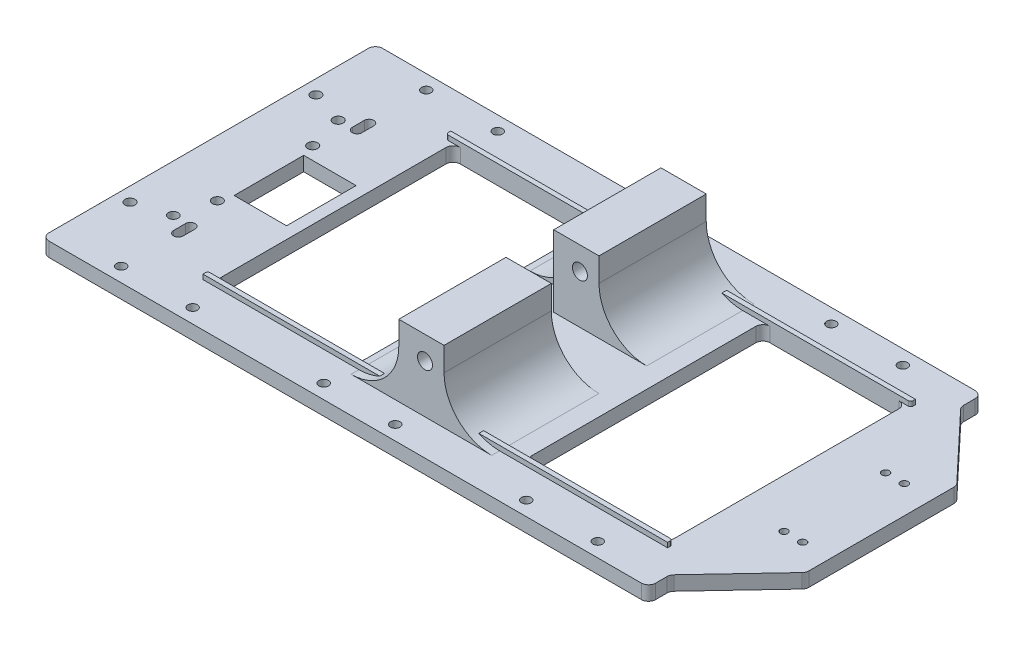
SolidWorks part; units mm, degrees
ref_plane "前视基准面" through (0, 0, 0) normal (0, 0, 1) x (1, 0, 0)
ref_plane "上视基准面" through (0, 0, 0) normal (0, 1, 0) x (1, 0, 0)
ref_plane "右视基准面" through (0, 0, 0) normal (1, 0, 0) x (0, 0, -1)
sketch "草图1" plane through (0, 0, 0) normal (0, 1, 0) x (1, 0, 0)
  line L0 (4082.7289, 1509.8503) -> (4060.7289, 1509.8503)
  line L1 (4175.7346, 1460.2503) -> (4175.7346, 1455.2395)
  line L2 (4145.7346, 1460.2503) -> (4145.7346, 1455.2395)
  line L3 (4179.7346, 1455.2395) -> (4179.7346, 1460.2503)
  line L4 (4115.6347, 1530.6257) -> (4120.1638, 1528.0129)
  line L5 (4060.7289, 1480.6503) -> (4082.7289, 1480.6503)
  line L6 (4094.7346, 1455.2395) -> (4094.7346, 1460.2503)
  line L7 (4149.7346, 1455.2395) -> (4149.7346, 1460.2503)
  line L8 (4122.2625, 1531.6509) -> (4117.7334, 1534.2637)
  line L9 (4060.7346, 1460.2503) -> (4060.7346, 1455.2395)
  line L10 (4234.7346, 1455.2395) -> (4234.7346, 1460.2503)
  line L11 (4064.7346, 1455.2395) -> (4064.7346, 1460.2503)
  line L12 (4090.7346, 1460.2503) -> (4090.7346, 1455.2395)
  line L13 (4060.7289, 1509.8503) -> (4060.7289, 1480.6503)
  line L14 (4082.7289, 1480.6503) -> (4082.7289, 1509.8503)
  line L15 (4090.7346, 1530.2503) -> (4090.7346, 1535.2611)
  line L16 (4176.5776, 1504.5503) -> (4176.5776, 1485.9503)
  line L17 (4175.5776, 1484.9503) -> (4135.5776, 1484.9503)
  line L18 (4094.7346, 1535.2611) -> (4094.7346, 1530.2503)
  line L19 (4115.7772, 1460.3388) -> (4120.3279, 1462.5177)
  line L20 (4149.7346, 1535.2611) -> (4149.7346, 1530.2503)
  line L21 (4060.7346, 1530.2503) -> (4060.7346, 1535.2611)
  line L22 (4145.7346, 1530.2503) -> (4145.7346, 1535.2611)
  line L23 (4122.1349, 1458.8376) -> (4117.6283, 1456.569)
  line L24 (4134.5776, 1485.9503) -> (4134.5776, 1504.5503)
  line L25 (4135.5776, 1505.5503) -> (4175.5776, 1505.5503)
  line L26 (4064.7346, 1535.2611) -> (4064.7346, 1530.2503)
  line L27 (4175.7346, 1530.2503) -> (4175.7346, 1535.2611)
  line L28 (4038.4346, 1425.2395) -> (4287.0345, 1425.2395)
  line L29 (4317.7347, 1464.8467) -> (4317.7347, 1525.6539)
  line L30 (4251.291, 1514.7632) -> (4251.291, 1522.5539)
  line L31 (4251.291, 1542.4908) -> (4251.291, 1550.2815)
  line L32 (4260.7346, 1460.2503) -> (4260.7346, 1455.2395)
  line L33 (4264.7346, 1455.2395) -> (4264.7346, 1460.2503)
  line L34 (4287.0345, 1565.2611) -> (4038.4346, 1565.2611)
  line L35 (4248.191, 1550.2815) -> (4248.191, 1542.4908)
  line L36 (4035.4346, 1562.2611) -> (4035.4346, 1428.2395)
  line L37 (4316.9188, 1527.7105) -> (4290.8504, 1555.3947)
  line L38 (4290.0345, 1557.4513) -> (4290.0345, 1562.2611)
  line L39 (4290.8504, 1435.106) -> (4316.9188, 1462.7901)
  line L40 (4248.191, 1522.5539) -> (4248.191, 1514.7632)
  line L41 (4230.7346, 1460.2503) -> (4230.7346, 1455.2395)
  line L42 (4290.0345, 1428.2395) -> (4290.0345, 1433.0493)
  line L43 (4256.0776, 1504.5503) -> (4256.0776, 1485.9503)
  line L44 (4230.7346, 1530.2503) -> (4230.7346, 1535.2611)
  line L45 (4260.7346, 1530.2503) -> (4260.7346, 1535.2611)
  line L46 (4255.0776, 1484.9503) -> (4215.0776, 1484.9503)
  line L47 (4215.0776, 1505.5503) -> (4255.0776, 1505.5503)
  line L48 (4179.7346, 1535.2611) -> (4179.7346, 1530.2503)
  line L49 (4248.191, 1467.9468) -> (4248.191, 1475.7374)
  line L50 (4234.7346, 1535.2611) -> (4234.7346, 1530.2503)
  line L51 (4214.0776, 1485.9503) -> (4214.0776, 1504.5503)
  line L52 (4248.191, 1440.2192) -> (4248.191, 1448.0098)
  line L53 (4251.291, 1475.7374) -> (4251.291, 1467.9468)
  line L54 (4264.7346, 1535.2611) -> (4264.7346, 1530.2503)
  line L55 (4251.291, 1448.0098) -> (4251.291, 1440.2192)
  arc A0 (4149.7346, 1460.2503) -> (4145.7346, 1460.2503) centre (4147.7346, 1460.2503) ccw
  arc A1 (4175.7346, 1455.2395) -> (4179.7346, 1455.2395) centre (4177.7346, 1455.2395) ccw
  arc A2 (4060.7346, 1455.2395) -> (4064.7346, 1455.2395) centre (4062.7346, 1455.2395) ccw
  circle A3 centre (4041.3063, 1456.3883) radius 2.1
  arc A4 (4064.7346, 1460.2503) -> (4060.7346, 1460.2503) centre (4062.7346, 1460.2503) ccw
  arc A5 (4179.7346, 1460.2503) -> (4175.7346, 1460.2503) centre (4177.7346, 1460.2503) ccw
  arc A6 (4090.7346, 1455.2395) -> (4094.7346, 1455.2395) centre (4092.7346, 1455.2395) ccw
  arc A7 (4230.7346, 1455.2395) -> (4234.7346, 1455.2395) centre (4232.7346, 1455.2395) ccw
  arc A8 (4117.7334, 1534.2637) -> (4115.6347, 1530.6257) centre (4116.6841, 1532.4447) ccw
  circle A9 centre (4055.2132, 1460.6687) radius 2.05
  arc A10 (4145.7346, 1455.2395) -> (4149.7346, 1455.2395) centre (4147.7346, 1455.2395) ccw
  circle A11 centre (4041.3063, 1534.3883) radius 2.1
  arc A12 (4094.7346, 1460.2503) -> (4090.7346, 1460.2503) centre (4092.7346, 1460.2503) ccw
  circle A13 centre (4055.2132, 1529.8319) radius 2.1
  circle A14 centre (4059.1243, 1515.2233) radius 2.1
  circle A15 centre (4059.1243, 1475.2233) radius 2.1
  arc A16 (4120.1638, 1528.0129) -> (4122.2625, 1531.6509) centre (4121.2132, 1529.8319) ccw
  arc A17 (4149.7346, 1535.2611) -> (4145.7346, 1535.2611) centre (4147.7346, 1535.2611) ccw
  arc A18 (4134.5776, 1485.9503) -> (4135.5776, 1484.9503) centre (4135.5776, 1485.9503) ccw
  arc A19 (4122.1349, 1458.8376) -> (4120.3279, 1462.5177) centre (4121.2132, 1460.6687) ccw
  arc A20 (4094.7346, 1535.2611) -> (4090.7346, 1535.2611) centre (4092.7346, 1535.2611) ccw
  arc A21 (4145.7346, 1530.2503) -> (4149.7346, 1530.2503) centre (4147.7346, 1530.2503) ccw
  arc A22 (4064.7346, 1535.2611) -> (4060.7346, 1535.2611) centre (4062.7346, 1535.2611) ccw
  circle A23 centre (4298.1991, 1473.9374) radius 1.55
  arc A24 (4060.7346, 1530.2503) -> (4064.7346, 1530.2503) centre (4062.7346, 1530.2503) ccw
  arc A25 (4175.5776, 1484.9503) -> (4176.5776, 1485.9503) centre (4175.5776, 1485.9503) ccw
  arc A26 (4115.7772, 1460.3388) -> (4117.6283, 1456.569) centre (4116.6841, 1458.4447) ccw
  circle A27 centre (4262.7346, 1559.2611) radius 2
  arc A28 (4090.7346, 1530.2503) -> (4094.7346, 1530.2503) centre (4092.7346, 1530.2503) ccw
  circle A29 centre (4306.0131, 1516.5632) radius 1.55
  circle A30 centre (4259.8276, 1500.2503) radius 1.6
  arc A31 (4176.5776, 1504.5503) -> (4175.5776, 1505.5503) centre (4175.5776, 1504.5503) ccw
  circle A32 centre (4298.1991, 1516.5632) radius 1.55
  circle A33 centre (4262.7346, 1431.2395) radius 2
  circle A34 centre (4306.0131, 1473.9374) radius 1.55
  arc A35 (4135.5776, 1505.5503) -> (4134.5776, 1504.5503) centre (4135.5776, 1504.5503) ccw
  arc A36 (4290.0345, 1562.2611) -> (4287.0345, 1565.2611) centre (4287.0345, 1562.2611) ccw
  arc A37 (4248.191, 1514.7632) -> (4251.291, 1514.7632) centre (4249.741, 1514.7632) ccw
  arc A38 (4038.4346, 1565.2611) -> (4035.4346, 1562.2611) centre (4038.4346, 1562.2611) ccw
  arc A39 (4264.7346, 1460.2503) -> (4260.7346, 1460.2503) centre (4262.7346, 1460.2503) ccw
  arc A40 (4317.7347, 1525.6539) -> (4316.9188, 1527.7105) centre (4314.7347, 1525.6539) ccw
  arc A41 (4234.7346, 1460.2503) -> (4230.7346, 1460.2503) centre (4232.7346, 1460.2503) ccw
  arc A42 (4248.191, 1542.4908) -> (4251.291, 1542.4908) centre (4249.741, 1542.4908) ccw
  arc A43 (4290.0345, 1557.4513) -> (4290.8504, 1555.3947) centre (4293.0345, 1557.4513) ccw
  arc A44 (4251.291, 1522.5539) -> (4248.191, 1522.5539) centre (4249.741, 1522.5539) ccw
  arc A45 (4035.4346, 1428.2395) -> (4038.4346, 1425.2395) centre (4038.4346, 1428.2395) ccw
  arc A46 (4251.291, 1550.2815) -> (4248.191, 1550.2815) centre (4249.741, 1550.2815) ccw
  arc A47 (4287.0345, 1425.2395) -> (4290.0345, 1428.2395) centre (4287.0345, 1428.2395) ccw
  arc A48 (4290.8504, 1435.106) -> (4290.0345, 1433.0493) centre (4293.0345, 1433.0493) ccw
  arc A49 (4316.9188, 1462.7901) -> (4317.7347, 1464.8467) centre (4314.7347, 1464.8467) ccw
  arc A50 (4260.7346, 1455.2395) -> (4264.7346, 1455.2395) centre (4262.7346, 1455.2395) ccw
  arc A51 (4234.7346, 1535.2611) -> (4230.7346, 1535.2611) centre (4232.7346, 1535.2611) ccw
  arc A52 (4214.0776, 1485.9503) -> (4215.0776, 1484.9503) centre (4215.0776, 1485.9503) ccw
  arc A53 (4260.7346, 1530.2503) -> (4264.7346, 1530.2503) centre (4262.7346, 1530.2503) ccw
  arc A54 (4230.7346, 1530.2503) -> (4234.7346, 1530.2503) centre (4232.7346, 1530.2503) ccw
  arc A55 (4255.0776, 1484.9503) -> (4256.0776, 1485.9503) centre (4255.0776, 1485.9503) ccw
  arc A56 (4179.7346, 1535.2611) -> (4175.7346, 1535.2611) centre (4177.7346, 1535.2611) ccw
  arc A57 (4215.0776, 1505.5503) -> (4214.0776, 1504.5503) centre (4215.0776, 1504.5503) ccw
  arc A58 (4256.0776, 1504.5503) -> (4255.0776, 1505.5503) centre (4255.0776, 1504.5503) ccw
  arc A59 (4251.291, 1475.7374) -> (4248.191, 1475.7374) centre (4249.741, 1475.7374) ccw
  arc A60 (4175.7346, 1530.2503) -> (4179.7346, 1530.2503) centre (4177.7346, 1530.2503) ccw
  arc A61 (4251.291, 1448.0098) -> (4248.191, 1448.0098) centre (4249.741, 1448.0098) ccw
  arc A62 (4264.7346, 1535.2611) -> (4260.7346, 1535.2611) centre (4262.7346, 1535.2611) ccw
  arc A63 (4248.191, 1467.9468) -> (4251.291, 1467.9468) centre (4249.741, 1467.9468) ccw
  arc A64 (4248.191, 1440.2192) -> (4251.291, 1440.2192) centre (4249.741, 1440.2192) ccw
  circle A65 centre (4147.7346, 1559.2611) radius 2
  circle A66 centre (4232.7346, 1559.2611) radius 2
  circle A67 centre (4210.3276, 1500.2503) radius 1.6
  circle A68 centre (4101.3063, 1456.3883) radius 2.1
  circle A69 centre (4163.6841, 1458.4447) radius 2.1
  circle A70 centre (4133.2132, 1525.2503) radius 2.1
  circle A71 centre (4163.6841, 1532.4447) radius 2.1
  circle A72 centre (4101.3063, 1534.3883) radius 2.1
  circle A73 centre (4177.7346, 1431.2395) radius 2
  circle A74 centre (4155.2132, 1525.2503) radius 2.1
  circle A75 centre (4155.2132, 1465.2503) radius 2.1
  circle A76 centre (4130.8276, 1490.2503) radius 1.6
  circle A77 centre (4117.1639, 1516.3492) radius 1.5
  circle A78 centre (4181.1639, 1474.3492) radius 1.5
  circle A79 centre (4133.2132, 1465.2503) radius 2.1
  circle A80 centre (4062.7346, 1559.2611) radius 2
  circle A81 centre (4180.3276, 1490.2503) radius 1.6
  circle A82 centre (4099.1243, 1515.2233) radius 2.1
  circle A83 centre (4099.1243, 1475.2233) radius 2.1
  circle A84 centre (4181.1639, 1516.2592) radius 1.5
  circle A85 centre (4259.8276, 1490.2503) radius 1.6
  circle A86 centre (4147.7346, 1431.2395) radius 2
  circle A87 centre (4177.7346, 1559.2611) radius 2
  circle A88 centre (4130.8276, 1500.2503) radius 1.6
  circle A89 centre (4210.3276, 1490.2503) radius 1.6
  circle A90 centre (4180.3276, 1500.2503) radius 1.6
  circle A91 centre (4092.7346, 1559.2611) radius 2
  circle A92 centre (4117.1639, 1474.3492) radius 1.5
  circle A93 centre (4249.741, 1457.9783) radius 6
  circle A94 centre (4232.7346, 1431.2395) radius 2
  circle A95 centre (4092.7346, 1431.2395) radius 2
  circle A96 centre (4062.7346, 1431.2395) radius 2
  dimension "D1" = 140.0216
extrude "凸台-拉伸1" add sketch "草图1" along normal blind 6
sketch "草图3" plane through (0, 6, 0) normal (0, 1, 0) x (1, 0, 0)
  line L1 (4084.8148, 1551.9432) -> (4288.3985, 1551.9432)
  line L2 (4084.8148, 1551.9432) -> (4084.8148, 1435.8117)
  line L3 (4084.8148, 1435.8117) -> (4288.3985, 1435.8117)
  line L4 (4288.3985, 1551.9432) -> (4288.3985, 1435.8117)
extrude "凸台-拉伸2" add sketch "草图3" against normal blind 6 contours L4 L1 L2 L3 | L1 region at (4186.6066, 6, -1493.8775)
sketch "草图4" plane through (0, 6, 0) normal (0, 1, 0) x (1, 0, 0)
  line L1 (4317.7347, 1464.8467) -> (4317.7347, 1525.6539) construction
  line L2 (4090.7347, 1545.5452) -> (4144.7347, 1545.5452)
  line L3 (4087.7347, 1542.5452) -> (4087.7347, 1448.5452)
  line L4 (4090.7347, 1445.5452) -> (4144.7347, 1445.5452)
  line L5 (4147.7347, 1542.5452) -> (4147.7347, 1448.5452)
  line L7 (4220.7347, 1545.5452) -> (4274.7347, 1545.5452)
  line L8 (4217.7347, 1542.5452) -> (4217.7347, 1448.5452)
  line L9 (4220.7347, 1445.5452) -> (4274.7347, 1445.5452)
  line L10 (4277.7347, 1542.5452) -> (4277.7347, 1448.5452)
  arc A0 (4147.7347, 1448.5452) -> (4144.7347, 1445.5452) centre (4144.7347, 1448.5452) cw
  arc A1 (4090.7347, 1445.5452) -> (4087.7347, 1448.5452) centre (4090.7347, 1448.5452) cw
  arc A2 (4087.7347, 1542.5452) -> (4090.7347, 1545.5452) centre (4090.7347, 1542.5452) cw
  arc A3 (4144.7347, 1545.5452) -> (4147.7347, 1542.5452) centre (4144.7347, 1542.5452) cw
  arc A4 (4220.7347, 1445.5452) -> (4217.7347, 1448.5452) centre (4220.7347, 1448.5452) cw
  arc A5 (4277.7347, 1448.5452) -> (4274.7347, 1445.5452) centre (4274.7347, 1448.5452) cw
  arc A6 (4277.7347, 1542.5452) -> (4274.7347, 1545.5452) centre (4274.7347, 1542.5452) ccw
  arc A7 (4220.7347, 1545.5452) -> (4217.7347, 1542.5452) centre (4220.7347, 1542.5452) ccw
  point P8 (4147.7347, 1445.5452)
  point P13 (4087.7347, 1545.5452)
  point P16 (4147.7347, 1545.5452)
  point P23 (4217.7347, 1445.5452)
  point P26 (4277.7347, 1445.5452)
  dimension "D4" = 3
  dimension "D7" = 3
  dimension "D1" = 60
  dimension "D2" = 170
  dimension "D3" = 100
  dimension "D5" = 70
  dimension "D6" = 60
extrude "切除-拉伸1" cut sketch "草图4" against normal through all both and the other way through all
sketch "草图6" plane through (0, 6, 0) normal (0, 1, 0) x (1, 0, 0)
  line L0 (4087.7347, 1542.5452) -> (4087.7347, 1448.5452) construction
  line L1 (4085.7347, 1545.5452) -> (4278.7347, 1545.5452)
  line L2 (4084.7347, 1546.5452) -> (4084.7347, 1547.5452)
  line L3 (4084.7347, 1547.5452) -> (4279.7347, 1547.5452)
  line L4 (4279.7347, 1546.5452) -> (4279.7347, 1547.5452)
  line L5 (4277.7347, 1448.5452) -> (4277.7347, 1542.5452) construction
  line L6 (4087.7347, 1495.5452) -> (4196.6431, 1495.5452) construction
  line L7 (4279.7347, 1444.5452) -> (4279.7347, 1443.5452)
  line L8 (4084.7347, 1443.5452) -> (4279.7347, 1443.5452)
  line L9 (4084.7347, 1444.5452) -> (4084.7347, 1443.5452)
  line L10 (4085.7347, 1445.5452) -> (4278.7347, 1445.5452)
  arc A0 (4279.7347, 1546.5452) -> (4278.7347, 1545.5452) centre (4278.7347, 1546.5452) cw
  arc A1 (4085.7347, 1545.5452) -> (4084.7347, 1546.5452) centre (4085.7347, 1546.5452) cw
  arc A2 (4085.7347, 1445.5452) -> (4084.7347, 1444.5452) centre (4085.7347, 1444.5452) ccw
  arc A3 (4279.7347, 1444.5452) -> (4278.7347, 1445.5452) centre (4278.7347, 1444.5452) ccw
  point P10 (4279.7347, 1545.5452)
  point P23 (4279.7347, 1445.5452)
  dimension "D4" = 1
  dimension "D1" = 3
  dimension "D2" = 2
  dimension "D3" = 2
extrude "凸台-拉伸3" add sketch "草图6" along normal blind 2
sketch "草图8" plane through (0, 6, 0) normal (0, 1, 0) x (1, 0, 0)
  line L0 (4287.0345, 1565.2611) -> (4038.4346, 1565.2611) construction
  line L1 (4173.2347, 1440.2395) -> (4189.2347, 1440.2395)
  line L2 (4173.2347, 1440.2395) -> (4173.2347, 1485.2395)
  line L3 (4173.2347, 1485.2395) -> (4189.2347, 1485.2395)
  line L4 (4189.2347, 1440.2395) -> (4189.2347, 1485.2395)
  line L5 (4173.2347, 1505.2611) -> (4189.2347, 1505.2611)
  line L6 (4173.2347, 1505.2611) -> (4173.2347, 1550.2611)
  line L7 (4173.2347, 1550.2611) -> (4189.2347, 1550.2611)
  line L8 (4189.2347, 1505.2611) -> (4189.2347, 1550.2611)
  line L9 (4038.4346, 1425.2395) -> (4287.0345, 1425.2395) construction
  line L10 (4317.7347, 1464.8467) -> (4317.7347, 1525.6539) construction
  dimension "D1" = 16
  dimension "D2" = 16
  dimension "D3" = 45
  dimension "D4" = 15
  dimension "D5" = 45
  dimension "D6" = 15
  dimension "D7" = 128.5
  dimension "D8" = 128.5
extrude "凸台-拉伸4" add sketch "草图8" along normal blind 30
sketch "草图9" plane through (0, 0, -1550.2611) normal (0, 0, -1) x (-1, 0, 0)
  line L0 (-4287.0345, 6) -> (-4038.4346, 6) construction
  line L1 (-4189.2347, 36) -> (-4189.2347, 31)
  line L2 (-4189.2347, 36) -> (-4189.2347, 6) construction
  line L3 (-4189.2347, 31) -> (-4189.2347, 26)
  line L4 (-4150.2347, 6) -> (-4151.8799, 6)
  line L5 (-4151.8799, 6) -> (-4176.2347, 6)
  line L6 (-4173.2347, 31) -> (-4173.2347, 36)
  line L7 (-4173.2347, 36) -> (-4173.2347, 6) construction
  line L8 (-4168.4605, 17.7647) -> (-4168.2936, 17.7647)
  line L9 (-4189.2347, 31) -> (-4173.2347, 31)
  line L10 (-4170.2347, 36) -> (-4170.2347, 26)
  line L11 (-4189.2347, 36) -> (-4173.2347, 36) construction
  line L13 (-4170.2347, 26) -> (-4170.2347, 31)
  line L15 (-4209.2347, 6) -> (-4215.2033, 6)
  line L16 (-4209.2347, 6) -> (-4151.8799, 6)
  line L17 (-4189.2347, 31) -> (-4173.2347, 31)
  line L19 (-4173.2347, 36) -> (-4170.2347, 36)
  line L20 (-4173.2347, 36) -> (-4173.2347, 31)
  line L22 (-4170.2347, 36) -> (-4170.2347, 31)
  arc A0 (-4150.2347, 6) -> (-4170.2347, 26) centre (-4150.2347, 26) cw
  arc A1 (-4209.2347, 6) -> (-4189.2347, 26) centre (-4209.2347, 26) ccw
  point P17 (-4189.2347, 6)
  point P28 (-4189.2347, 6)
  line M2 (-4173.2347, 6) -> (-4173.2347, 36)
  line M4 (-4189.2347, 36) -> (-4189.2347, 6)
  dimension "D1" = 20
  dimension "D2" = 20
  dimension "D3" = 3
extrude "凸台-拉伸5" add sketch "草图9" against normal through all contours L5 M2 | L8 M4 region at (4193.7021, 10.4674, -1550.2611) region at (4168.8216, 15.8582, -1550.2611)
sketch "草图10" plane through (0, 6, 0) normal (0, 1, 0) x (1, 0, 0)
  line L0 (4038.4346, 1425.2395) -> (4150.2347, 1425.2395) construction
  line L1 (4161.2347, 1425.2395) -> (4204.2347, 1425.2395)
  line L2 (4161.2347, 1440.2395) -> (4161.2347, 1443.5452)
  line L4 (4204.2347, 1440.2395) -> (4204.2347, 1443.5452)
  line L5 (4200.5169, 1443.5452) -> (4279.7347, 1443.5452) construction
  line L6 (4204.2347, 1425.2395) -> (4204.2347, 1443.5452) construction
  line L7 (4161.2347, 1445.5452) -> (4161.2347, 1545.5452) construction
  line L8 (4161.2347, 1485.2395) -> (4204.2347, 1485.2395)
  line L10 (4161.2347, 1505.2611) -> (4204.2347, 1505.2611)
  line L12 (4204.2347, 1445.5452) -> (4204.2347, 1545.5452) construction
  line L13 (4161.2347, 1440.2395) -> (4204.2347, 1440.2395)
  line L14 (4150.2347, 1445.5452) -> (4150.2347, 1545.5452) construction
  line L15 (4161.2347, 1505.2611) -> (4150.2347, 1505.2611)
  line L16 (4161.2347, 1485.2395) -> (4161.2347, 1484.9503)
  line L18 (4150.2347, 1505.2611) -> (4150.2347, 1484.9503)
  line L19 (4150.2347, 1425.2395) -> (4150.2347, 1443.5452) construction
  line L20 (4204.2347, 1505.2611) -> (4209.7379, 1505.2611)
  line L22 (4204.2347, 1485.2395) -> (4209.7379, 1485.2395)
  line L23 (4209.7379, 1505.2611) -> (4209.7379, 1485.2395)
  line L24 (4161.2347, 1440.2395) -> (4150.2347, 1440.2395)
  line L26 (4161.2347, 1425.2395) -> (4150.2347, 1425.2395)
  line L27 (4150.2347, 1440.2395) -> (4150.2347, 1425.2395)
  line L28 (4189.2347, 1425.2395) -> (4209.2347, 1425.2395) construction
  line L29 (4204.2347, 1440.2395) -> (4209.2654, 1440.2395)
  line L31 (4204.2347, 1425.2395) -> (4209.2654, 1425.2395)
  line L32 (4209.2654, 1440.2395) -> (4209.2654, 1425.2395)
  line L33 (4161.2347, 1485.2395) -> (4150.2347, 1485.2395)
extrude "切除-拉伸2" cut sketch "草图10" along normal through all contours L13 L2 L1 L4 | L8 L10 region at (4179.7501, 6, -1432.7395) region at (4179.9863, 6, -1495.2503)
sketch "草图12" plane through (0, 0, -1550.2611) normal (0, 0, -1) x (-1, 0, 0)
  line L0 (-4287.0345, 6) -> (-4038.4346, 6) construction
  line L1 (-4189.2347, 36) -> (-4189.2347, 26) construction
  circle A0 centre (-4181.2347, 26.3) radius 3.15
  dimension "D1" = 6.3
  dimension "D2" = 20.3
  dimension "D3" = 8
extrude "切除-拉伸4" cut sketch "草图12" against normal through all
sketch "草图13" plane through (0, 6, 0) normal (0, 1, 0) x (1, 0, 0)
  line L0 (4150.2347, 1445.5452) -> (4150.2347, 1485.2395) construction
  line L1 (4150.2347, 1475.2395) -> (4170.2347, 1475.2395)
  line L2 (4150.2347, 1475.2395) -> (4150.2347, 1485.2395)
  line L3 (4150.2347, 1485.2395) -> (4170.2347, 1485.2395)
  line L4 (4170.2347, 1475.2395) -> (4170.2347, 1485.2395)
  line L5 (4170.2347, 1440.2395) -> (4170.2347, 1485.2395) construction
  line L6 (4170.2347, 1485.2395) -> (4150.2347, 1485.2395) construction
  line L7 (4150.2347, 1505.2611) -> (4170.2347, 1505.2611) construction
  line L8 (4150.2347, 1505.2611) -> (4170.2347, 1505.2611)
  line L9 (4150.2347, 1505.2611) -> (4150.2347, 1515.2611)
  line L10 (4150.2347, 1515.2611) -> (4170.2347, 1515.2611)
  line L11 (4170.2347, 1505.2611) -> (4170.2347, 1515.2611)
  line L12 (4170.2347, 1505.2611) -> (4170.2347, 1550.2611) construction
  line L13 (4207.6492, 1505.2611) -> (4207.6492, 1485.2395) construction
  line L14 (4207.6492, 1505.2611) -> (4209.2347, 1505.2611)
  line L15 (4207.6492, 1505.2611) -> (4207.6492, 1485.2395)
  line L16 (4207.6492, 1485.2395) -> (4209.2347, 1485.2395)
  line L17 (4209.2347, 1505.2611) -> (4209.2347, 1485.2395)
  line L18 (4209.2347, 1445.5452) -> (4209.2347, 1485.2395) construction
  dimension "D1" = 10
  dimension "D2" = 10
extrude "切除-拉伸5" cut sketch "草图13" along normal through all
sketch "草图11" plane through (0, 0, -1550.2611) normal (0, 0, -1) x (-1, 0, 0)
  line L1 (-4287.0345, 6) -> (-4038.4346, 6) construction
  line L2 (-4189.2347, 36) -> (-4189.2347, 26) construction
  circle A0 centre (-4181.2347, 26.3) radius 3.15
  circle A1 centre (-4152.8879, 26) radius 3
  dimension "D1" = 6.3
  dimension "D2" = 8
  dimension "D3" = 20
  dimension "D4" = 20.3
